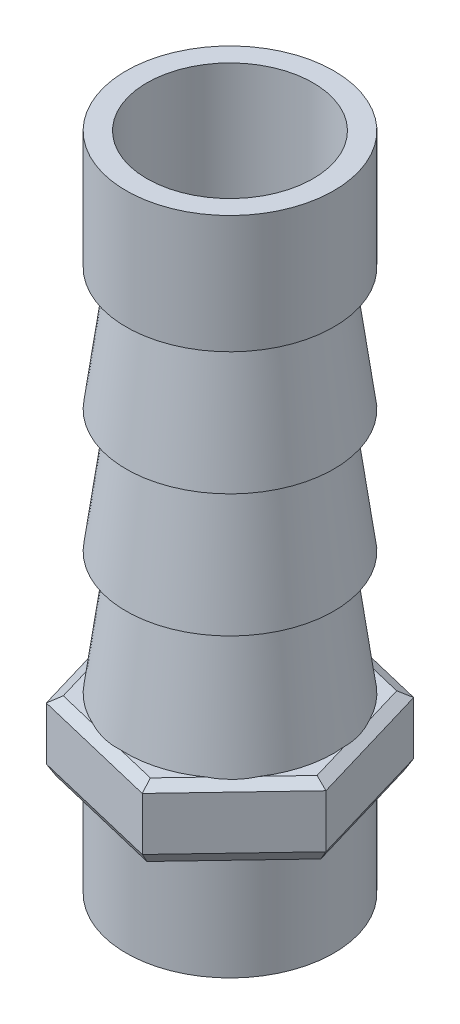
SolidWorks part; units mm, degrees
ref_plane "Front Plane" through (0, 0, 0) normal (0, 0, 1) x (1, 0, 0)
ref_plane "Top Plane" through (0, 0, 0) normal (0, 1, 0) x (1, 0, 0)
ref_plane "Right Plane" through (0, 0, 0) normal (1, 0, 0) x (0, 0, -1)
sketch "草图2" plane through (0, 0, 0) normal (0, 0, 1) x (1, 0, 0)
  line L0 (0, 0) -> (-3, 0)
  line L20 (-3, 23.0231) -> (0, 23.0231)
  line L25 (-3, 0) -> (-2.5249, 3.5545)
  line L26 (-2.5249, 3.5545) -> (-3, 3.5545)
  line L27 (-3, 3.5545) -> (-2.5249, 7.1089)
  line L28 (-2.5249, 7.1089) -> (-3, 7.1089)
  line L29 (-3, 7.1089) -> (-2.5249, 10.6634)
  line L30 (-2.5249, 10.6634) -> (-3, 10.6634)
  line L31 (-3, 10.6634) -> (-3, 14.0724)
  line L32 (-3, 14.0724) -> (0, 14.0724)
  line L34 (0, 0) -> (0, 14.0724)
revolve "旋转3" add sketch "草图2" angle 360 about L34
sketch "草图4" plane through (0, 0, 0) normal (0, -1, 0) x (1, 0, 0)
  line L1 (2.5845, -2.721) -> (3.6487, 0.8777)
  line L2 (3.6487, 0.8777) -> (1.0642, 3.5987)
  line L3 (1.0642, 3.5987) -> (-2.5845, 2.721)
  line L4 (-2.5845, 2.721) -> (-3.6487, -0.8777)
  line L5 (-3.6487, -0.8777) -> (-1.0642, -3.5987)
  line L6 (-1.0642, -3.5987) -> (2.5845, -2.721)
extrude "凸台-拉伸1" add sketch "草图4" along normal blind 2
chamfer "倒角1" distance 0.3 angle 30 12 edges at (-2.3565, -2, -2.2382) (-3.1166, -2, 0.9217) (-0.7601, -2, 3.1599) (2.3565, -2, 2.2382) (3.1166, -2, -0.9217) (0.7601, -2, -3.1599) (-0.7601, 0, 3.1599) (-3.1166, 0, 0.9217) (-2.3565, 0, -2.2382) (0.7601, 0, -3.1599) (3.1166, 0, -0.9217) (2.3565, 0, 2.2382)
sketch "草图5" plane through (0, -2, 0) normal (0, -1, 0) x (1, 0, 0)
  circle A0 centre (0, 0) radius 3
extrude "凸台-拉伸2" add sketch "草图5" along normal blind 3 contours A0
sketch "草图6" plane through (0, 14.0724, 0) normal (0, 1, 0) x (1, 0, 0)
  circle A0 centre (0, 0) radius 2.4
extrude "切除-拉伸3" cut sketch "草图6" against normal blind 15 contours A0
scale "缩放比例1" scale about centroid uniform scaling yes scale factor 3
